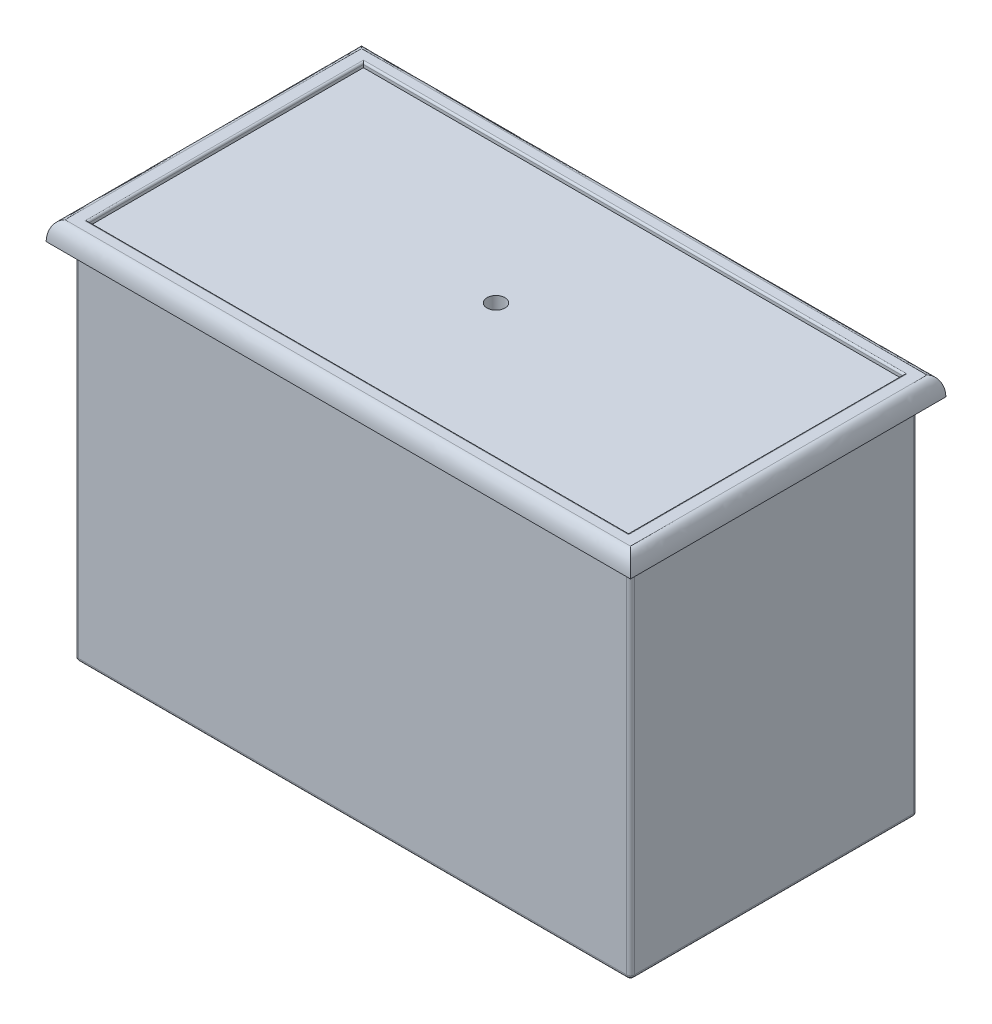
SolidWorks part; units mm, degrees
ref_plane "Front Plane" through (0, 0, 0) normal (0, 0, 1) x (1, 0, 0)
ref_plane "Top Plane" through (0, 0, 0) normal (0, 1, 0) x (1, 0, 0)
ref_plane "Right Plane" through (0, 0, 0) normal (1, 0, 0) x (0, 0, -1)
sketch "Sketch2" plane through (0, 0, 0) normal (0, 1, 0) x (1, 0, 0)
  line L0 (-290.5, 148.5) -> (290.5, 148.5)
  line L1 (-293.5, 151.5) -> (293.5, 151.5)
  line L2 (-293.5, 151.5) -> (-293.5, -151.5)
  line L3 (-293.5, -151.5) -> (293.5, -151.5)
  line L4 (293.5, 151.5) -> (293.5, -151.5)
  line L5 (-293.5, 151.5) -> (293.5, -151.5) construction
  line L6 (-293.5, -151.5) -> (293.5, 151.5) construction
  line L7 (290.5, 148.5) -> (290.5, -148.5)
  line L8 (-290.5, -148.5) -> (290.5, -148.5)
  line L9 (-290.5, 148.5) -> (-290.5, -148.5)
  point P0 (0, 0)
  dimension "D1" = 303
  dimension "D2" = 587
  dimension "D3" = 3
extrude "Walls" add sketch "Sketch2" along normal blind 380 contours L0 L7 L8 L9 | L2 L1 L4 L3
sketch "Sketch3" plane through (0, 0, 0) normal (0, -1, 0) x (1, 0, 0)
  line L1 (293.5, 151.5) -> (-293.5, 151.5)
  line L2 (293.5, 151.5) -> (293.5, -151.5)
  line L3 (293.5, -151.5) -> (-293.5, -151.5)
  line L4 (-293.5, 151.5) -> (-293.5, -151.5)
  line L5 (293.5, 151.5) -> (-293.5, -151.5) construction
  line L6 (293.5, -151.5) -> (-293.5, 151.5) construction
  point P0 (0, 0)
extrude "Base" add sketch "Sketch3" along normal blind 3
sketch "Sketch5" plane through (0, 380, 0) normal (0, 1, 0) x (1, 0, 0)
  line L8 (-308.5, -166.5) -> (308.5, -166.5)
  line L9 (-308.5, 166.5) -> (-308.5, -166.5)
  line L10 (308.5, -166.5) -> (308.5, 166.5)
  line L11 (308.5, 166.5) -> (-308.5, 166.5)
  line L12 (-308.5, -166.5) -> (308.5, -166.5)
  line L13 (-308.5, 166.5) -> (-308.5, -166.5)
  line L14 (308.5, -166.5) -> (308.5, 166.5)
  line L15 (308.5, 166.5) -> (-308.5, 166.5)
  dimension "D1" = 15
extrude "Lid" add sketch "Sketch5" along normal blind 20
sketch "Sketch7" plane through (0, 400, 0) normal (0, 1, 0) x (1, 0, 0)
  line L1 (-285, 145) -> (285, 145)
  line L2 (-285, 145) -> (-285, -145)
  line L3 (-285, -145) -> (285, -145)
  line L4 (285, 145) -> (285, -145)
  line L5 (-285, 145) -> (285, -145) construction
  line L6 (-285, -145) -> (285, 145) construction
  point P0 (0, 0)
  dimension "D1" = 570
  dimension "D2" = 290
extrude "Lid Divet" cut sketch "Sketch7" against normal blind 5
fillet "Fillet1" radius 20 4 edges at (0, 400, -166.5) (308.5, 400, 0) (0, 400, 166.5) (-308.5, 400, 0) second distance 10 first distance on face at (0, 390, -166.5) first distance on face at (308.5, 390, 0) first distance on face at (0, 390, 166.5) first distance on face at (-308.5, 390, 0)
fillet "Fillet2" radius 2 4 edges at (285, 400, 0) (0, 400, 145) (-285, 400, 0) (0, 400, -145)
fillet "Fillet3" radius 4 8 edges at (0, -3, 151.5) (293.5, -3, 0) (0, -3, -151.5) (-293.5, -3, 0) (293.5, 188.5, -151.5) (293.5, 188.5, 151.5) (-293.5, 188.5, -151.5) (-293.5, 188.5, 151.5)
sketch "Sketch8" plane through (0, 395, 0) normal (0, 1, 0) x (1, 0, 0)
  circle A0 centre (0, 0) radius 9.525
  dimension "D1" = 19.05
extrude "Inlet" cut sketch "Sketch8" against normal up to next
sketch "Sketch9" plane through (0, -3, 0) normal (0, -1, 0) x (1, 0, 0)
  line L0 (-289.5, 147.5) -> (-289.5, -147.5) construction
  circle A0 centre (-259.5, 0) radius 9.525
  point P5 (0, 0)
  dimension "D1" = 19.05
  dimension "D2" = 30
extrude "Cut-Extrude3" cut sketch "Sketch9" against normal up to next
equation "\"D1@Walls\" = 390 - 10"
